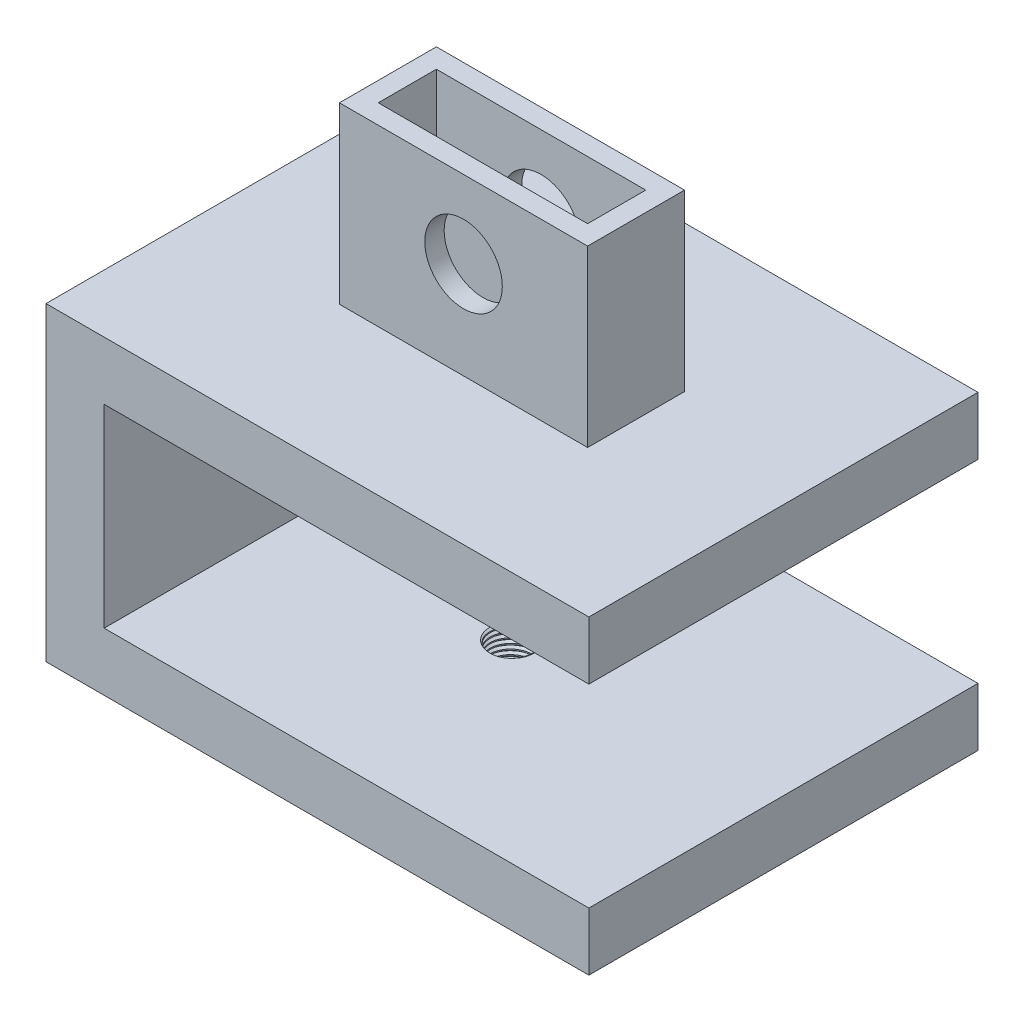
SolidWorks part; units mm, degrees
material "AISI 1020"
ref_plane "Front Plane" through (0, 0, 0) normal (0, 0, 1) x (1, 0, 0)
ref_plane "Top Plane" through (0, 0, 0) normal (0, 1, 0) x (1, 0, 0)
ref_plane "Right Plane" through (0, 0, 0) normal (1, 0, 0) x (0, 0, -1)
sketch "Sketch1" plane through (0, 0, 0) normal (0, 1, 0) x (1, 0, 0)
  line L1 (-70, -50.1762) -> (70, -50.1762)
  line L2 (-70, -50.1762) -> (-70, 50.1762)
  line L3 (-70, 50.1762) -> (70, 50.1762)
  line L4 (70, -50.1762) -> (70, 50.1762)
  line L5 (-70, -50.1762) -> (70, 50.1762) construction
  line L6 (-70, 50.1762) -> (70, -50.1762) construction
  point P0 (0, 0)
  dimension "D1" = 140
  dimension "D2" = 100.3523
extrude "Boss-Extrude1" add sketch "Sketch1" along normal blind 80
sketch "Sketch2" plane through (0, 0, 0) normal (0, 0, 1) x (1, 0, 0)
  line L0 (0, 0) -> (0, 50000) construction
  line L1 (-70, 0) -> (70, 0) construction
  line L2 (0, 0) -> (50000, 0) construction
  line L3 (-43.3702, 65) -> (-55, 65)
  line L4 (-55, 65) -> (-55, 15)
  line L5 (-55, 15) -> (70, 15)
  line L6 (70, 80) -> (70, 0) construction
  line L7 (70, 15) -> (70, 65)
  line L8 (70, 65) -> (-43.3702, 65)
  line L9 (-70, 80) -> (70, 80) construction
  line L10 (-70, 80) -> (-70, 0) construction
  point P4 (0, 0)
  dimension "D1" = 15
  dimension "D2" = 15
  dimension "D3" = 15
extrude "Cut-Extrude1" cut sketch "Sketch2" against normal blind 80 and the other way blind 80
sketch "Sketch3" plane through (0, 0, 0) normal (0, 1, 0) x (1, 0, 0)
  circle A0 centre (0, 0) radius 5.45
  dimension "D1" = 10.9
extrude "Cut-Extrude2" cut sketch "Sketch3" along normal blind 37
sketch "Sketch4" plane through (0, 0, 0) normal (0, 1, 0) x (1, 0, 0)
  line L0 (-32, 12.5) -> (32, 12.5)
  line L1 (-27, -7.5) -> (27, -7.5)
  line L2 (-27, -7.5) -> (-27, 7.5)
  line L3 (-27, 7.5) -> (27, 7.5)
  line L4 (27, -7.5) -> (27, 7.5)
  line L5 (-27, -7.5) -> (27, 7.5) construction
  line L6 (-27, 7.5) -> (27, -7.5) construction
  line L7 (32, -12.5) -> (32, 12.5)
  line L8 (-32, -12.5) -> (32, -12.5)
  line L9 (-32, -12.5) -> (-32, 12.5)
  point P0 (0, 0)
  dimension "D1" = 54
  dimension "D2" = 15
  dimension "D3" = 5
extrude "Boss-Extrude2" add sketch "Sketch4" along normal blind 45 from surface at 80 starting at face at (0, 80, 0)
sketch "Sketch5" plane through (0, 0, 12.5) normal (0, 0, 1) x (1, 0, 0)
  line L0 (0, 117) -> (0, -49883) construction
  line L3 (-32, 80) -> (32, 80) construction
  line L4 (-32, 125) -> (32, 125) construction
  circle A0 centre (0, 105) radius 10
  point P12 (0, 125)
  dimension "D1" = 20
  dimension "D2" = 25
extrude "Cut-Extrude3" cut sketch "Sketch5" against normal blind 37
sketch "Sketch6" plane through (70, 0, 0) normal (1, 0, 0) x (0, 0, -1)
  line L0 (0, 0) -> (0, 25) construction
  dimension "D1" = 25
thread "Thread1" pitch 1.25 profile "Thread Profile1" start angle 0, offset 0, length 90, pitch 1.25, diameter 10.9
ref_plane "Plane1" through (-5.45, 25, 0) normal (0, 0, 1) x (-1, 0, 0)
sketch "Thread Profile1" plane through (-5.45, 25, 0) normal (0, 0, 1) x (-1, 0, 0)
  line L0 (0, 0) -> (0, 1.25) construction
  line L1 (0, 0) -> (0.6766, 0.3906)
  line L2 (0.6766, 0.3906) -> (0.6766, 0.5469)
  line L3 (0.6766, 0.5469) -> (0, 0.9375)
  line L4 (0.6766, 0.4687) -> (0, 0.4687) construction
  line L11 (0, 0) -> (0, 0.9375)
  point P2 (0, 0)
  dimension "Pitch" = 1.25
  dimension "Profile_Angle" = 60
  dimension "Profile_Land" = 0.1562
  dimension "Profile_Height" = 0.6766
